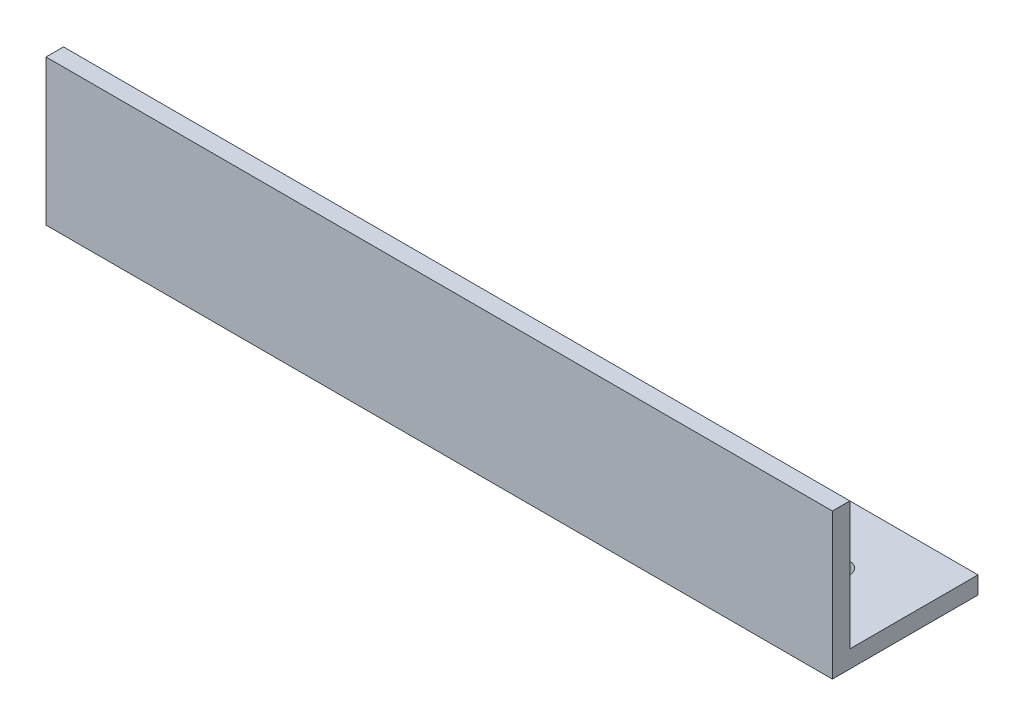
SolidWorks part; units mm, degrees
ref_plane "Спереди" through (0, 0, 0) normal (0, 0, 1) x (1, 0, 0)
ref_plane "Сверху" through (0, 0, 0) normal (0, 1, 0) x (1, 0, 0)
ref_plane "Справа" through (0, 0, 0) normal (1, 0, 0) x (0, 0, -1)
sketch "Эскиз1" plane through (0, 0, 0) normal (1, 0, 0) x (0, 0, -1)
  line L0 (0, 0) -> (50, 0)
  line L5 (0, 50) -> (0, 0)
extrude "Вытянуть-Тонкостенный2" add sketch "Эскиз1" along normal blind 270 thin thin type one direction reverse wall 6
sketch "Эскиз2" plane through (0, 0, 0) normal (0, -1, 0) x (1, 0, 0)
  line L0 (135, 0) -> (135, -56.3824) construction
  line L1 (270, 0) -> (0, 0) construction
  circle A0 centre (26, -28) radius 4
  circle A1 centre (244, -28) radius 4
extrude "Вырез-Вытянуть1" cut sketch "Эскиз2" against normal through all
